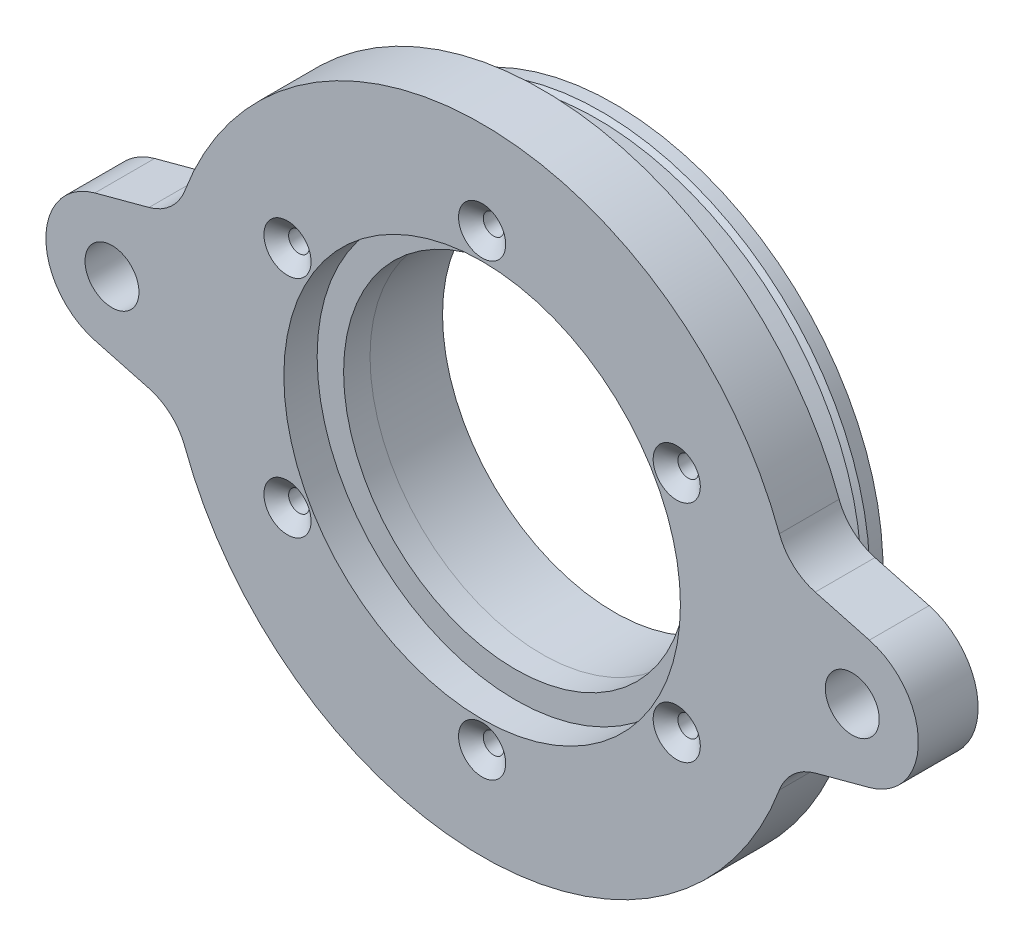
SolidWorks part; units mm, degrees
material "6061-T6 (SS)"
ref_plane "Front Plane" through (0, 0, 0) normal (0, 0, 1) x (1, 0, 0)
ref_plane "Top Plane" through (0, 0, 0) normal (0, 1, 0) x (1, 0, 0)
ref_plane "Right Plane" through (0, 0, 0) normal (1, 0, 0) x (0, 0, -1)
sketch "Sketch1" plane through (0, 0, 0) normal (1, 0, 0) x (0, 0, -1)
  line L0 (0, 0) -> (-40.6014, 0) construction
  line L1 (4.5145, 63.5) -> (0, 50.389)
  line L2 (0, 50.389) -> (-4.5145, 63.5)
  line L3 (0, 66.548) -> (44.1437, 66.548)
  line L4 (-4.5145, 63.5) -> (-19.0509, 63.5)
  line L5 (-4.5145, 63.5) -> (-5.5305, 64.516)
  line L6 (-5.5305, 64.516) -> (-19.3119, 64.516)
  line L7 (-0.9636, 53.1876) -> (0.9636, 53.1876)
  line L8 (-8.7055, 64.516) -> (-8.7055, 41.275)
  line L9 (-8.7055, 41.275) -> (0, 41.275)
  line L10 (0, 41.275) -> (0, 53.1876)
  circle A0 centre (0, 62.5793) radius 3.9687
  dimension "D2" = 7.9375
  dimension "D1" = 38
  dimension "D3" = 133.096
  dimension "D4" = 127
  dimension "D5" = 45
  dimension "D6" = 1.016
  dimension "D7" = 10.3124
  dimension "D8" = 3.175
  dimension "D9" = 82.55
revolve "Revolve1" add sketch "Sketch1" angle 360 about L0 region at (0, 51.17, 4.867) region at (0, 52.2547, 0.3212) region at (0, 63.9846, 6.8523)
mirror "Mirror1" about plane through (0, 0, 0) normal (0, 0, -1) of "Revolve1"
sketch "Sketch2" plane through (0, 0, 8.7055) normal (0, 0, 1) x (1, 0, 0)
  line L0 (0, 0) -> (88.9, 0)
  line L1 (0, 0) -> (-88.9, 0)
  line L2 (-93.0088, 15.3341) -> (-73.3632, 20.5981)
  line L3 (-93.0088, -15.3341) -> (-73.3632, -20.5981)
  line L4 (93.0088, -15.3341) -> (73.3632, -20.5981)
  line L5 (93.0088, 15.3341) -> (73.3632, 20.5981)
  circle A0 centre (0, 0) radius 76.2
  circle A2 centre (0, 0) radius 47.625
  circle A3 centre (-88.9, 0) radius 6.477
  circle A4 centre (88.9, 0) radius 6.477
  circle A5 centre (-88.9, 0) radius 15.875
  circle A6 centre (88.9, 0) radius 15.875
  circle M2 centre (0, 0) radius 64.516
  dimension "D1" = 152.4
  dimension "D2" = 95.25
  dimension "D4" = 12.954
  dimension "D5" = 31.75
  dimension "D3" = 88.9
  dimension "D6" = 30
  dimension "D7" = 30
extrude "Boss-Extrude1" add sketch "Sketch2" along normal blind 14.351 contours A2 L1 L0 M2 | A6 L0 L1 A5 A0 M2 | A6 A0 L4 | A6 A0 A4 | L0 A6 A0 | A0 A6 L0 | A6 A0 A5 L1 L0 M2 | A6 L5 A0 | A5 A0 L2 | A0 A5 A3 | A5 L3 A0 | L1 A5 A0 | A0 A5 L1 | A2 L0 L1 M2 region at (0, 49.0676, 8.7055) region at (56.0705, -1.4426, 8.7055) region at (0, 66.2108, 8.7055) region at (68.7705, -1.6948, 8.7055) region at (74.8182, 3.3356, 8.7055) region at (74.8182, -3.3356, 8.7055) region at (-74.8182, -3.3356, 8.7055) region at (-74.8182, 3.3356, 8.7055) region at (76.5022, 4.4341, 8.7055) region at (79.1261, 15.8333, 8.7055) region at (79.1261, -15.8333, 8.7055) region at (-76.5022, -4.4341, 8.7055) region at (-79.1261, 15.8333, 8.7055) region at (-79.1261, -15.8333, 8.7055)
fillet "Fillet2" radius 12.7 4 edges at (73.3632, -20.5981, 15.881) (73.3632, 20.5981, 15.881) (-73.3632, 20.5981, 15.881) (-73.3632, -20.5981, 15.881)
sketch "Sketch3" plane through (0, 0, 8.7055) normal (0, 0, 1) x (1, 0, 0)
  circle A0 centre (0, 0) radius 41.275 construction
  circle A1 centre (0, 0) radius 47.625 construction
  circle A2 centre (0, 0) radius 41.275
  circle A3 centre (0, 0) radius 47.625
extrude "Boss-Extrude2" add sketch "Sketch3" along normal blind 6.35
ref_plane "Plane1" through (0, 0, 8.7055) normal (0, 0, -1) x (-1, 0, 0)
sketch "Sketch4" plane through (0, 0, 23.0565) normal (0, 0, 1) x (1, 0, 0)
  circle A0 centre (0, 0) radius 53.975
  circle A1 centre (0, 0) radius 47.625 construction
  circle A2 centre (0, 53.975) radius 2.4892
  dimension "D1" = 6.35
  dimension "D2" = 4.9784
extrude "Cut-Extrude1" cut sketch "Sketch4" against normal blind 22.225 contours A2
chamfer "Chamfer1" distance 3.175 angle 41 1 edges at (2.4892, 53.975, 23.0565) first distance on face at (2.4892, 53.975, 23.0565)
pattern_circular "CirPattern1" count 6 over 360 about axis through (0, 0, 23.0565) along (0, 0, 1) of "Cut-Extrude1", "Chamfer1"
split "Split1" trim tools "Plane1" bodies to split 106 resulting bodies 107 108
